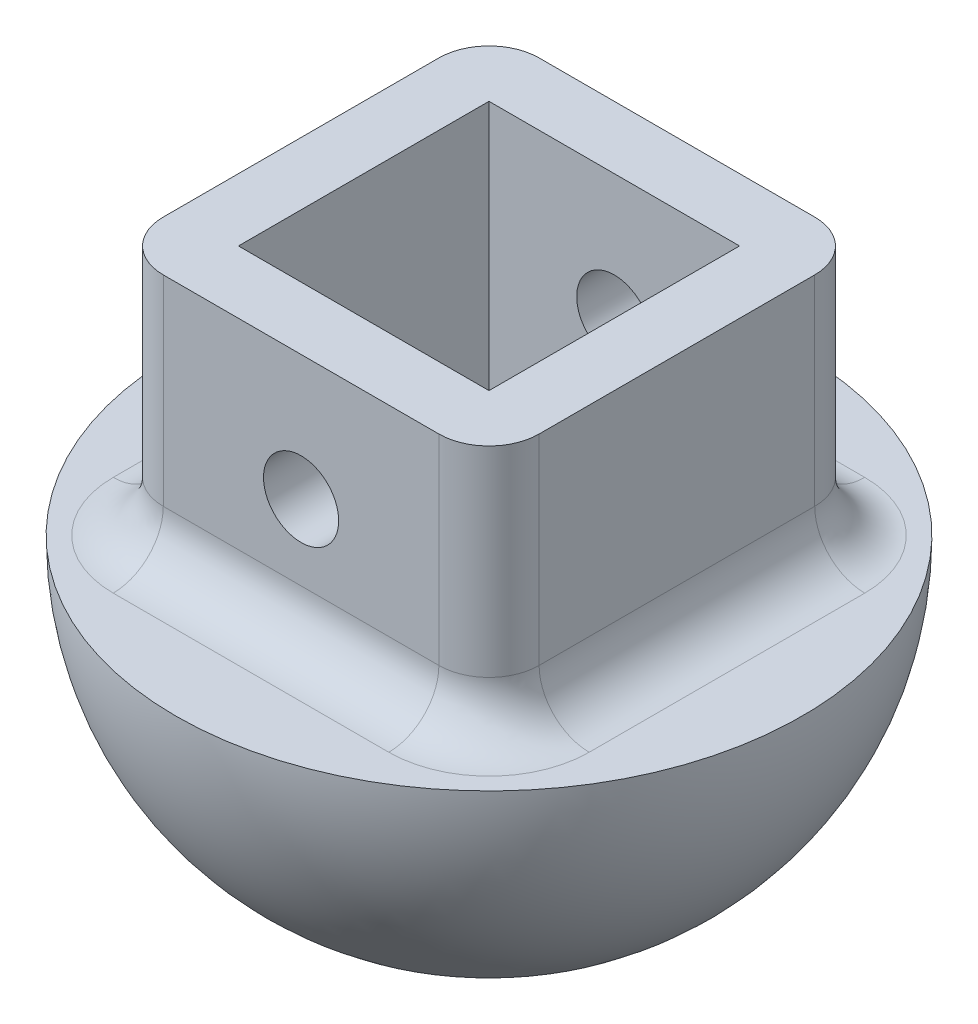
SolidWorks part; units mm, degrees
ref_plane "Front Plane" through (0, 0, 0) normal (0, 0, 1) x (1, 0, 0)
ref_plane "Top Plane" through (0, 0, 0) normal (0, 1, 0) x (1, 0, 0)
ref_plane "Right Plane" through (0, 0, 0) normal (1, 0, 0) x (0, 0, -1)
sketch "Sketch4" plane through (0, 0, 0) normal (0, 1, 0) x (1, 0, 0)
  line L0 (-12.5, 0) -> (12.5, 0)
  arc A0 (-12.5, 0) -> (12.5, 0) centre (0, 0) ccw
  point P2 (0, 0)
  point P5 (3.7132, 0)
  point P6 (0, 0)
  point P8 (0, 0)
  point P9 (6.9243, 0)
  point P10 (0, 0)
  dimension "D1" = 25
revolve "Revolve2" add sketch "Sketch4" angle 180 about L0 region at (0, 0, 5.3052)
sketch "Sketch1" plane through (0, 0, 0) normal (0, 1, 0) x (1, 0, 0)
  line L1 (-5, 5) -> (5, 5)
  line L2 (-5, 5) -> (-5, -5)
  line L3 (-5, -5) -> (5, -5)
  line L4 (5, 5) -> (5, -5)
  line L5 (-5, 5) -> (5, -5) construction
  line L6 (-5, -5) -> (5, 5) construction
  line L7 (-7.5, 7.5) -> (7.5, 7.5)
  line L8 (-7.5, 7.5) -> (-7.5, -7.5)
  line L9 (-7.5, -7.5) -> (7.5, -7.5)
  line L10 (7.5, 7.5) -> (7.5, -7.5)
  line L11 (-7.5, 7.5) -> (7.5, -7.5) construction
  line L12 (-7.5, -7.5) -> (7.5, 7.5) construction
  point P0 (0, 0)
  point P6 (0, 0)
  dimension "D1" = 10
  dimension "D2" = 15
extrude "Boss-Extrude1" add sketch "Sketch1" along normal blind 10
sketch "Sketch2" plane through (0, 0, 5) normal (0, 0, -1) x (-1, 0, 0)
  line L0 (0, 0) -> (0, 10) construction
  line L1 (-7.5, 10) -> (7.5, 10) construction
  circle A0 centre (0, 5) radius 1.5
  dimension "D1" = 3
extrude "Cut-Extrude1" cut sketch "Sketch2" against normal blind 10 and the other way blind 20
fillet "Fillet1" radius 2 8 edges at (-7.5, 5, 7.5) (-7.5, 5, -7.5) (7.5, 5, -7.5) (7.5, 5, 7.5) (0, 0, -7.5) (7.5, 0, 0) (-7.5, 0, 0) (0, 0, 7.5)
